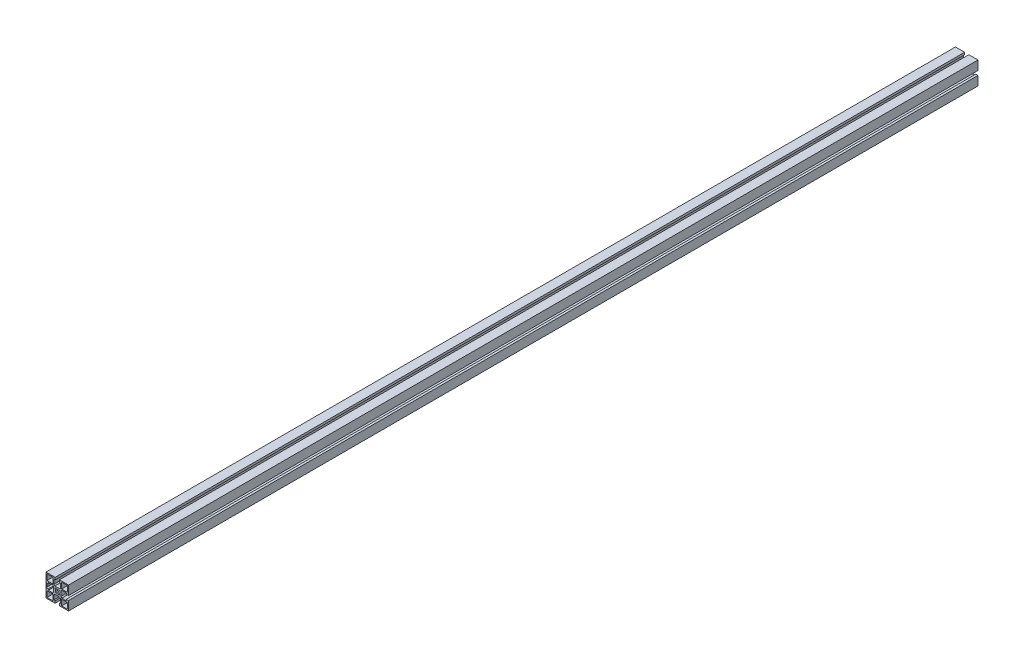
SolidWorks part; units mm, degrees
material "6061 Alloy"
ref_plane "Front Plane" through (0, 0, 0) normal (0, 0, 1) x (1, 0, 0)
ref_plane "Top Plane" through (0, 0, 0) normal (0, 1, 0) x (1, 0, 0)
ref_plane "Right Plane" through (0, 0, 0) normal (1, 0, 0) x (0, 0, -1)
sketch "Sketch1" plane through (0, 0, 0) normal (0, 0, 1) x (1, 0, 0)
  line L0 (-4.2495, 22.1993) -> (-4.2495, 22.4993)
  line L1 (-4.2495, 22.4993) -> (-4.2495, 22.1993)
  line L2 (4.2505, 22.1993) -> (4.2505, 22.4993)
  line L3 (4.2505, 22.4993) -> (4.2505, 22.1993)
  line L4 (-22.1995, 4.2493) -> (-22.4995, 4.2493)
  line L5 (-22.1995, -4.2507) -> (-22.4995, -4.2507)
  line L6 (-4.2495, -22.2007) -> (-4.2495, -22.5007)
  line L7 (4.2505, -22.2007) -> (4.2505, -22.5007)
  line L8 (-22.4995, -22.5007) -> (22.5005, -22.5007)
  line L9 (22.5005, -22.5007) -> (22.5005, 22.4993)
  line L10 (22.5005, 22.4993) -> (-22.4995, 22.4993)
  line L11 (-22.4995, 22.4993) -> (-22.4995, -22.5007)
  line L12 (22.2005, -4.2507) -> (22.5005, -4.2507)
  line L13 (22.2005, 4.2493) -> (22.5005, 4.2493)
  line L24 (-20.4995, -20.5007) -> (-20.4995, -8.8007)
  line L25 (-8.7996, -20.5007) -> (-20.4995, -20.5007)
  line L26 (-8.7996, -8.8007) -> (-8.7996, -20.5007)
  line L27 (-20.4995, -8.8007) -> (-8.7996, -8.8007)
  line L28 (8.8005, -20.5008) -> (8.8005, -8.8008)
  line L29 (20.5005, -20.5008) -> (8.8005, -20.5008)
  line L30 (20.5005, -8.8008) -> (20.5005, -20.5008)
  line L31 (8.8005, -8.8008) -> (20.5005, -8.8008)
  line L32 (20.5006, 8.7993) -> (8.8006, 8.7993)
  line L33 (20.5006, 20.4993) -> (20.5006, 8.7993)
  line L34 (8.8006, 20.4993) -> (20.5006, 20.4993)
  line L35 (8.8006, 8.7993) -> (8.8006, 20.4993)
  line L36 (-8.7995, 20.4993) -> (-8.7995, 8.7993)
  line L37 (-8.7995, 8.7993) -> (-20.4995, 8.7993)
  line L38 (-20.4995, 8.7993) -> (-20.4995, 20.4993)
  line L39 (-20.4995, 20.4993) -> (-8.7995, 20.4993)
  line L54 (-22.1995, -3.9507) -> (-21.7318, -3.483)
  line L55 (-22.1995, -4.2507) -> (-22.1995, -3.9507)
  line L56 (-17.9995, -4.2507) -> (-22.1995, -4.2507)
  line L57 (-17.9995, -6.8007) -> (-17.9995, -4.2507)
  line L58 (-9.1995, -6.8007) -> (-17.9995, -6.8007)
  line L59 (-7.1995, -4.8007) -> (-9.1995, -6.8007)
  line L60 (-7.1995, 4.7993) -> (-7.1995, -4.8007)
  line L61 (-9.1995, 6.7993) -> (-7.1995, 4.7993)
  line L62 (-17.9995, 6.7993) -> (-9.1995, 6.7993)
  line L63 (-17.9995, 4.2493) -> (-17.9995, 6.7993)
  line L64 (-22.1995, 4.2493) -> (-17.9995, 4.2493)
  line L65 (-22.1995, 3.9493) -> (-22.1995, 4.2493)
  line L66 (-21.7317, 3.4815) -> (-22.1995, 3.9493)
  line L67 (-20.9995, -1.7152) -> (-20.9995, 1.7137)
  line L82 (-6.7995, -18.0007) -> (-6.7995, -9.2007)
  line L83 (-4.2495, -18.0007) -> (-6.7995, -18.0007)
  line L84 (-4.2495, -22.2007) -> (-4.2495, -18.0007)
  line L85 (-3.9495, -22.2007) -> (-4.2495, -22.2007)
  line L86 (-3.4817, -21.733) -> (-3.9495, -22.2007)
  line L87 (1.715, -21.0007) -> (-1.7139, -21.0007)
  line L88 (3.9505, -22.2007) -> (3.4828, -21.733)
  line L89 (4.2505, -22.2007) -> (3.9505, -22.2007)
  line L90 (4.2505, -18.0007) -> (4.2505, -22.2007)
  line L91 (6.8005, -18.0007) -> (4.2505, -18.0007)
  line L92 (6.8005, -9.2007) -> (6.8005, -18.0007)
  line L93 (4.8005, -7.2007) -> (6.8005, -9.2007)
  line L94 (-4.7995, -7.2007) -> (4.8005, -7.2007)
  line L95 (-6.7995, -9.2007) -> (-4.7995, -7.2007)
  line L110 (7.2005, -4.8007) -> (7.2005, 4.7993)
  line L111 (9.2005, -6.8007) -> (7.2005, -4.8007)
  line L112 (18.0005, -6.8007) -> (9.2005, -6.8007)
  line L113 (18.0005, -4.2507) -> (18.0005, -6.8007)
  line L114 (22.2005, -4.2507) -> (18.0005, -4.2507)
  line L115 (22.2005, -3.9507) -> (22.2005, -4.2507)
  line L116 (21.7327, -3.4829) -> (22.2005, -3.9507)
  line L117 (21.0005, 1.7138) -> (21.0005, -1.7151)
  line L118 (22.2005, 3.9493) -> (21.7328, 3.4816)
  line L119 (22.2005, 4.2493) -> (22.2005, 3.9493)
  line L120 (18.0005, 4.2493) -> (22.2005, 4.2493)
  line L121 (18.0005, 6.7993) -> (18.0005, 4.2493)
  line L122 (9.2005, 6.7993) -> (18.0005, 6.7993)
  line L123 (7.2005, 4.7993) -> (9.2005, 6.7993)
  line L138 (-4.7995, 7.1993) -> (-6.7995, 9.1993)
  line L139 (4.8005, 7.1993) -> (-4.7995, 7.1993)
  line L140 (6.8005, 9.1993) -> (4.8005, 7.1993)
  line L141 (6.8005, 17.9993) -> (6.8005, 9.1993)
  line L142 (4.2505, 17.9993) -> (6.8005, 17.9993)
  line L143 (4.2505, 22.1993) -> (4.2505, 17.9993)
  line L144 (3.9505, 22.1993) -> (4.2505, 22.1993)
  line L145 (3.4828, 21.7316) -> (3.9505, 22.1993)
  line L146 (-1.7139, 20.9993) -> (1.715, 20.9993)
  line L147 (-3.9495, 22.1993) -> (-3.4817, 21.7315)
  line L148 (-4.2495, 22.1993) -> (-3.9495, 22.1993)
  line L149 (-4.2495, 17.9993) -> (-4.2495, 22.1993)
  line L150 (-6.7995, 17.9993) -> (-4.2495, 17.9993)
  line L151 (-6.7995, 9.1993) -> (-6.7995, 17.9993)
  line L164 (-4.5957, -3.1827) -> (-3.2622, -1.8492)
  line L165 (-3.1815, -4.5969) -> (-4.5957, -3.1827)
  line L166 (-1.848, -3.2635) -> (-3.1815, -4.5969)
  line L167 (3.1825, -4.5969) -> (1.849, -3.2635)
  line L168 (4.5967, -3.1827) -> (3.1825, -4.5969)
  line L169 (3.2633, -1.8492) -> (4.5967, -3.1827)
  line L170 (4.5967, 3.1813) -> (3.2633, 1.8478)
  line L171 (3.1825, 4.5955) -> (4.5967, 3.1813)
  line L172 (1.849, 3.262) -> (3.1825, 4.5955)
  line L173 (-3.1815, 4.5955) -> (-1.848, 3.262)
  line L174 (-4.5957, 3.1813) -> (-3.1815, 4.5955)
  line L175 (-3.2622, 1.8478) -> (-4.5957, 3.1813)
  arc A2 (-21.7318, -3.483) -> (-20.9995, -1.7152) centre (-23.4995, -1.7152) ccw
  arc A3 (-20.9995, 1.7137) -> (-21.7317, 3.4815) centre (-23.4995, 1.7137) ccw
  arc A6 (-1.7139, -21.0007) -> (-3.4817, -21.733) centre (-1.7139, -23.5007) ccw
  arc A7 (3.4828, -21.733) -> (1.715, -21.0007) centre (1.715, -23.5007) ccw
  arc A10 (21.0005, -1.7151) -> (21.7327, -3.4829) centre (23.5005, -1.7151) ccw
  arc A11 (21.7328, 3.4816) -> (21.0005, 1.7138) centre (23.5005, 1.7138) ccw
  arc A14 (1.715, 20.9993) -> (3.4828, 21.7316) centre (1.715, 23.4993) ccw
  arc A15 (-3.4817, 21.7315) -> (-1.7139, 20.9993) centre (-1.7139, 23.4993) ccw
  arc A20 (-1.848, -3.2635) -> (1.849, -3.2635) centre (0.0005, -0.0007) ccw
  arc A21 (3.2633, -1.8492) -> (3.2633, 1.8478) centre (0.0005, -0.0007) ccw
  arc A22 (1.849, 3.262) -> (-1.848, 3.262) centre (0.0005, -0.0007) ccw
  arc A23 (-3.2622, 1.8478) -> (-3.2622, -1.8492) centre (0.0005, -0.0007) ccw
extrude "Boss-Extrude1" add sketch "Sketch1" along normal blind 1817.878 contours L138 L151 L150 L149 L0 L10 L11 L4 L64 L63 L62 L61 L60 L59 L58 L57 L56 L5 L8 L6 L84 L83 L82 L95 L94 L93 L92 L91 L90 L7 L9 L12 L114 L113 L112 L111 L110 L123 L122 L121 L120 L13 L2 L143 L142 L141 L140 | L147 A15 L146 A14 L145 L144 L2 L10 L0 L148 | L67 A3 L66 L65 L4 L11 L5 L55 L54 A2 region at (-4.8859, 20.0993, 0) region at (0.0005, 21.8242, 0) region at (-21.8244, -0.0007, 0)
extrude "Cut-Extrude1" cut sketch "Sketch1<4>" along normal up to next contours L147 A15 L146 A14 L145 L144 L2 L10 L0 L148 region at (0.0005, 21.8242, 0)
sketch "Sketch1<4>" plane through (0, 0, 0) normal (0, 0, 1) x (1, 0, 0) same geometry as "Sketch1"
